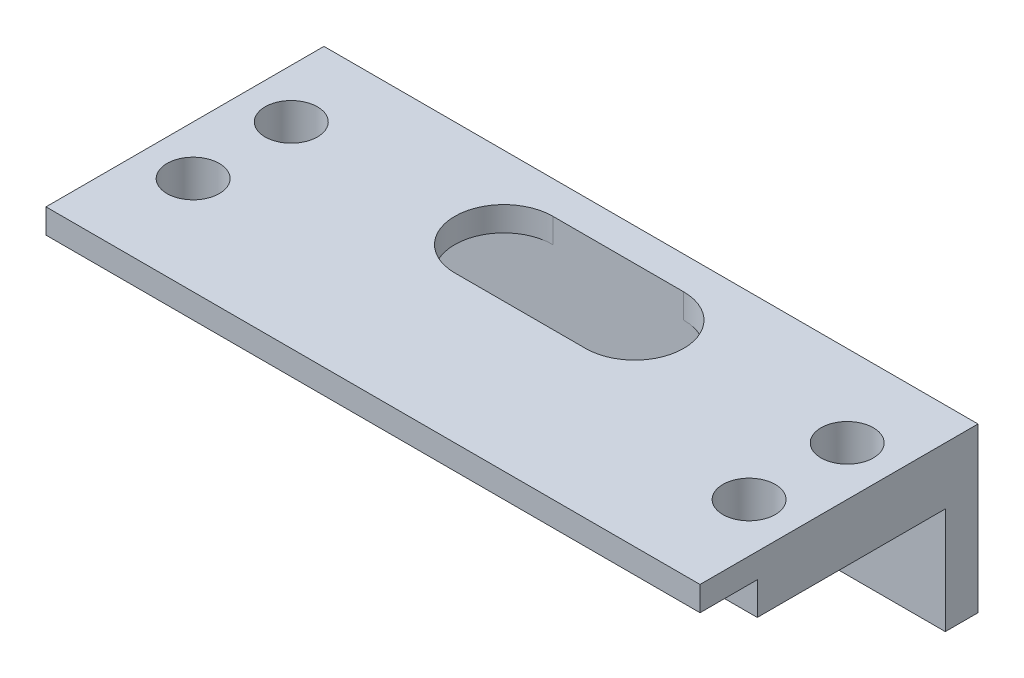
SolidWorks part; units mm, degrees
ref_plane "前视基准面" through (0, 0, 0) normal (0, 0, 1) x (1, 0, 0)
ref_plane "上视基准面" through (0, 0, 0) normal (0, 1, 0) x (1, 0, 0)
ref_plane "右视基准面" through (0, 0, 0) normal (1, 0, 0) x (0, 0, -1)
sketch "草图1" plane through (0, 0, 0) normal (1, 0, 0) x (0, 0, -1)
  line L0 (0, 0) -> (-15, 0)
  line L1 (-15, 0) -> (-15, 3.5)
  line L2 (-15, 3.5) -> (2, 3.5)
  line L3 (2, 3.5) -> (2, -6.5)
  line L4 (0, 0) -> (0, -6.5)
  line L5 (0, -6.5) -> (2, -6.5)
extrude "凸台-拉伸1" add sketch "草图1" along normal blind 40
sketch "草图2" plane through (0, 3.5, 0) normal (0, 1, 0) x (1, 0, 0)
  line L1 (24, 0) -> (16, 0)
  line L2 (16, -6) -> (24, -6)
  circle A0 centre (3, -3) radius 1.6
  circle A1 centre (3, -9) radius 1.6
  circle A2 centre (37, -9) radius 1.6
  circle A3 centre (37, -3) radius 1.6
  arc A8 (16, 0) -> (16, -6) centre (16, -3) ccw
  arc A9 (24, 0) -> (24, -6) centre (24, -3) cw
  point P16 (20, -5)
  point P18 (20, -6)
  point P22 (20, -1)
extrude "切除-拉伸1" cut sketch "草图2" against normal blind 10
sketch "草图3" plane through (0, 0, 0) normal (0, -1, 0) x (1, 0, 0)
  line L0 (3, 11.5) -> (0, 11.5)
  line L1 (0, 15) -> (0, 0) construction
  line L2 (5.5, 9) -> (5.5, 0)
  line L3 (40, 0) -> (24, 0) construction
  line L4 (5.5, 0) -> (34.5, 0)
  line L6 (34.5, 9) -> (34.5, 0)
  line L7 (37, 11.5) -> (40, 11.5)
  line L8 (40, 11.5) -> (40, 15)
  line L9 (40, 15) -> (0, 15)
  line L10 (0, 15) -> (0, 11.5)
  arc A0 (5.5, 9) -> (3, 11.5) centre (3, 9) ccw
  arc A1 (34.5, 9) -> (37, 11.5) centre (37, 9) cw
extrude "切除-拉伸2" cut sketch "草图3" against normal blind 2
